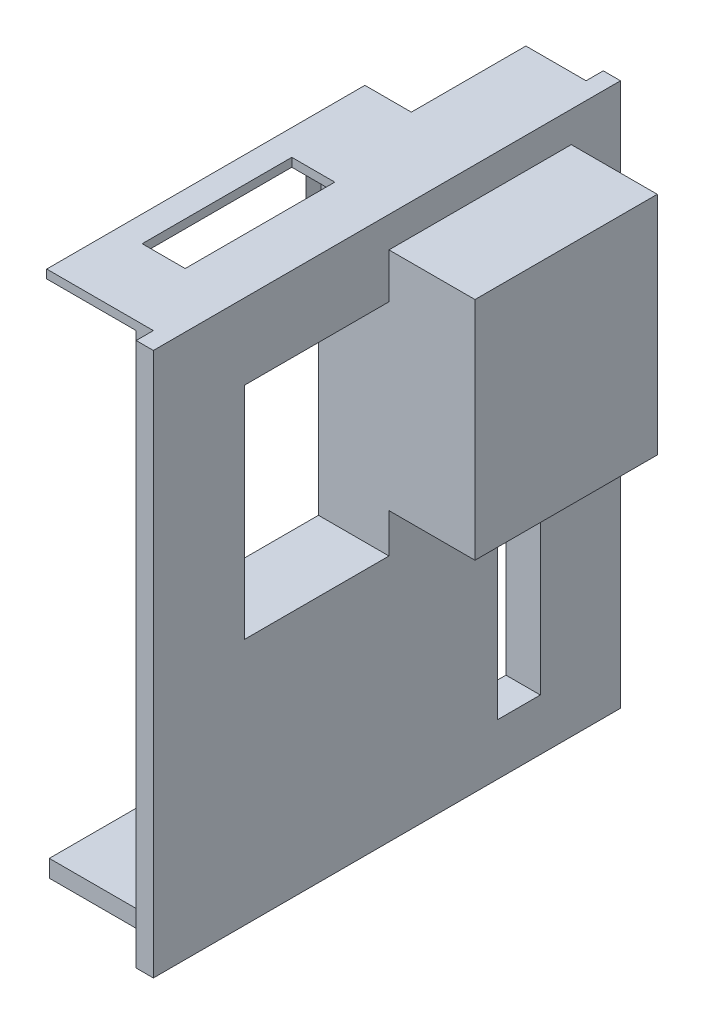
SolidWorks part; units mm, degrees
note: The reader was unsure of these and kept them because the rebuilt part matched: shared geometry of "Sketch1<7>", "Sketch1<9>", "Sketch5<3>", "Sketch5<4>".
ref_plane "Front Plane" through (0, 0, 0) normal (0, 0, 1) x (1, 0, 0)
ref_plane "Top Plane" through (0, 0, 0) normal (0, 1, 0) x (1, 0, 0)
ref_plane "Right Plane" through (0, 0, 0) normal (1, 0, 0) x (0, 0, -1)
sketch "Sketch1" plane through (0, 0, 0) normal (1, 0, 0) x (0, 0, -1)
  line L1 (-14.986, 38.735) -> (32.004, 38.735)
  line L3 (-31.9039, -38.989) -> (32.004, -38.989)
  line L4 (32.004, 38.735) -> (32.004, -38.989)
  line L6 (-31.9039, 38.735) -> (-31.9039, -38.989)
  line L8 (-34.4439, 32.3253) -> (-34.4439, -41.529)
  line L9 (-34.4439, -41.529) -> (34.544, -41.529)
  line L10 (34.544, 38.735) -> (34.544, -41.529)
  line L11 (-31.9039, 38.735) -> (15.0861, 38.735)
  line L12 (-14.986, 38.735) -> (32.004, 38.735)
  line L13 (-31.9039, 38.735) -> (-31.9039, 37.465)
  line L16 (-34.4439, 32.3253) -> (-34.4439, 38.735)
  line L18 (-14.986, 38.735) -> (-31.9039, 38.735)
  line L20 (-34.4439, 38.735) -> (-31.9039, 38.735)
  line L21 (32.004, 38.735) -> (34.544, 38.735)
  line L24 (32.004, 38.735) -> (32.004, 36.195)
  line L25 (-14.986, 38.735) -> (32.004, 38.735)
  line L28 (32.004, 38.735) -> (32.004, 36.195)
  line L29 (-31.9039, 37.465) -> (15.0861, 37.465)
  line L30 (15.0861, 38.735) -> (15.0861, 37.465)
  point P0 (0, 0)
  point P6 (0, 0)
  dimension "D1" = 77.724
  dimension "D2" = 63.9079
  dimension "D3" = 46.99
  dimension "D4" = 1.27
  dimension "D5" = 2.54
  dimension "D6" = 2.54
  dimension "D7" = 2.54
extrude "Boss-Extrude3" add sketch "Sketch1" along normal blind 2.54
extrude "Boss-Extrude4" add sketch "Sketch1<7>" against normal blind 2.54
sketch "Sketch1<7>" plane through (0, 0, 0) normal (1, 0, 0) x (0, 0, -1) same geometry as "Sketch1"
extrude "Boss-Extrude6" add sketch "Sketch1<9>" against normal blind 15.748 contours L13 L29 L30 L11
sketch "Sketch1<9>" plane through (0, 0, 0) normal (1, 0, 0) x (0, 0, -1) same geometry as "Sketch1"
sketch "Sketch2" plane through (0, 38.735, 0) normal (0, 1, 0) x (1, 0, 0)
  line L0 (-15.748, -31.9039) -> (-15.748, 15.0861) construction
  line L1 (-15.748, -21.6169) -> (-5.588, -21.6169)
  line L2 (-15.748, -21.6169) -> (-15.748, 0.4811)
  line L3 (-15.748, 0.4811) -> (-5.588, 0.4811)
  line L4 (-5.588, -21.6169) -> (-5.588, 0.4811)
  line L5 (-15.748, -31.9039) -> (0, -31.9039) construction
  line L6 (-11.938, 0.4811) -> (-11.938, -21.6169)
  dimension "D1" = 10.287
  dimension "D2" = 10.16
  dimension "D3" = 22.098
  dimension "D4" = 3.81
extrude "Cut-Extrude1" cut sketch "Sketch2" against normal blind 2.54 contours L3 L6 L1 L4
sketch "Sketch3" plane through (-2.54, 0, 0) normal (-1, 0, 0) x (0, 0, 1)
  line L1 (-32.004, 38.735) -> (-15.0861, 38.735)
  line L2 (-32.004, 38.735) -> (-32.004, 37.465)
  line L3 (-32.004, 37.465) -> (-15.0861, 37.465)
  line L4 (-15.0861, 38.735) -> (-15.0861, 37.465)
  dimension "D1" = 1.27
extrude "Boss-Extrude7" add sketch "Sketch3" along normal blind 6.35
sketch "Sketch4" plane through (2.54, 0, 0) normal (1, 0, 0) x (0, 0, -1)
  line L0 (-20.9819, 27.559) -> (-20.9819, 38.735) construction
  line L2 (-34.4439, 27.559) -> (-20.9819, 27.559) construction
  line L3 (-34.4439, -41.529) -> (-34.4439, 38.735) construction
  line L4 (-34.4439, 38.735) -> (34.544, 38.735) construction
  line L6 (-20.9819, 27.559) -> (0.3541, 27.559)
  line L7 (-20.9819, 27.559) -> (-20.9819, -4.953)
  line L8 (-20.9819, -4.953) -> (0.3541, -4.953)
  line L9 (0.3541, 27.559) -> (0.3541, -4.953)
  dimension "D1" = 11.176
  dimension "D2" = 13.462
  dimension "D3" = 32.512
  dimension "D4" = 21.336
extrude "Cut-Extrude2" cut sketch "Sketch4" against normal up to surface (5.08 mm away) up to face at (-2.54, -0.762, -0.05)
sketch "Sketch5" plane through (2.54, 0, 0) normal (1, 0, 0) x (0, 0, -1)
  line L0 (-34.4439, 33.401) -> (1.1161, 33.401) construction
  line L1 (-34.4439, -41.529) -> (-34.4439, 38.735) construction
  line L2 (1.1161, 33.401) -> (1.1161, 38.735) construction
  line L3 (-34.4439, 38.735) -> (34.544, 38.735) construction
  line L4 (1.1161, 1.651) -> (26.5161, 33.401) construction
  line L5 (1.1161, 33.401) -> (26.5161, 33.401)
  line L6 (1.1161, 33.401) -> (1.1161, 1.651)
  line L7 (1.1161, 1.651) -> (26.5161, 1.651)
  line L8 (26.5161, 33.401) -> (26.5161, 1.651)
  line L9 (1.1161, 33.401) -> (26.5161, 1.651) construction
  line L10 (0.3541, -4.953) -> (0.3541, 27.559) construction
  line L11 (27.2781, 34.1982) -> (0.3541, 34.1982)
  line L12 (27.2781, 34.1982) -> (27.2781, 0.8538)
  line L13 (27.2781, 0.8538) -> (0.3541, 0.8538)
  line L14 (0.3541, 34.1982) -> (0.3541, 0.8538)
  line L15 (27.2781, 34.1982) -> (0.3541, 0.8538) construction
  line L16 (27.2781, 0.8538) -> (0.3541, 34.1982) construction
  point P10 (13.8161, 17.526)
  dimension "D1" = 35.56
  dimension "D2" = 5.334
  dimension "D3" = 25.4
  dimension "D4" = 31.75
  dimension "D5" = 0.762
extrude "Cut-Extrude3" cut sketch "Sketch5" against normal up to surface (5.08 mm away) contours L8 L5 L6 L7 | L14 L13 L12 L11
extrude "Boss-Extrude8" add sketch "Sketch5<3>" along normal blind 12.7
sketch "Sketch5<3>" plane through (2.54, 0, 0) normal (1, 0, 0) x (0, 0, -1) same geometry as "Sketch5"
extrude "Boss-Extrude9" add sketch "Sketch5<4>" against normal blind 1.27 from offset 12.7 contours L8 L5 L6 L7
sketch "Sketch5<4>" plane through (2.54, 0, 0) normal (1, 0, 0) x (0, 0, -1) same geometry as "Sketch5"
sketch "Sketch7" plane through (-2.54, 0, 0) normal (-1, 0, 0) x (0, 0, 1)
  line L0 (-0.3541, 27.559) -> (-0.3541, -4.953) construction
  line L1 (21.7439, 28.321) -> (-1.1161, 28.321)
  line L2 (21.7439, 28.321) -> (21.7439, -5.715)
  line L3 (21.7439, -5.715) -> (-1.1161, -5.715)
  line L4 (-1.1161, 28.321) -> (-1.1161, -5.715)
  line L5 (-0.3541, -4.953) -> (20.9819, -4.953) construction
  line L6 (20.9819, -4.953) -> (20.9819, 27.559) construction
  line L7 (20.9819, 27.559) -> (-0.3541, 27.559) construction
  line L9 (-0.3541, 27.559) -> (20.9819, 27.559)
  line L10 (-0.3541, 27.559) -> (-0.3541, -4.953)
  line L11 (-0.3541, -4.953) -> (20.9819, -4.953)
  line L12 (20.9819, 27.559) -> (20.9819, -4.953)
  dimension "D1" = 0.762
  dimension "D2" = 0.762
  dimension "D3" = 0.762
  dimension "D4" = 0.762
extrude "Boss-Extrude10" add sketch "Sketch7" along normal blind 5.334
sketch "Sketch6" plane through (-2.54, 0, 0) normal (-1, 0, 0) x (0, 0, 1)
  line L0 (-32.004, 37.465) -> (-15.0861, 37.465) construction
  line L1 (-15.0861, 37.465) -> (-15.0861, -38.989) construction
  line L2 (31.9039, -38.989) -> (-32.004, -38.989) construction
  line L3 (-15.0861, -38.989) -> (-32.004, -38.989) construction
  line L4 (-32.004, -38.989) -> (-32.004, 37.465) construction
  line L5 (-15.0861, -38.989) -> (-32.004, -38.989) construction
  line L6 (-15.0861, -0.889) -> (-32.004, -0.889) construction
  line L12 (-23.545, -0.889) -> (-32.004, -0.889) construction
  line L13 (-32.004, -0.889) -> (-27.7745, -0.889) construction
  line L14 (-27.7745, -0.889) -> (-27.7745, -38.989) construction
  line L16 (-22.7061, -0.889) -> (-16.3561, -0.889)
  line L33 (-22.7061, -0.889) -> (-22.7061, -33.909)
  line L34 (-22.7061, -33.909) -> (-16.3561, -33.909)
  line L35 (-16.3561, -0.889) -> (-16.3561, -33.909)
  dimension "D1" = 1.27
  dimension "D2" = 6.35
  dimension "D3" = 33.02
  dimension "D4" = 38.1
ref_plane "Plane1" through (0, -0.889, 0) normal (0, 1, 0) x (1, 0, 0)
extrude "Cut-Extrude5" cut sketch "Sketch6" against normal blind 5.334
sketch "Sketch9" plane through (-2.54, 0, 0) normal (-1, 0, 0) x (0, 0, 1)
  line L1 (31.9039, -38.989) -> (-11.2761, -38.989)
  line L2 (31.9039, -38.989) -> (31.9039, -36.449)
  line L3 (31.9039, -36.449) -> (-11.2761, -36.449)
  line L4 (-11.2761, -38.989) -> (-11.2761, -36.449)
  dimension "D1" = 2.54
  dimension "D2" = 43.18
extrude "Boss-Extrude12" add sketch "Sketch9" along normal blind 12.827
sketch "Sketch10" plane through (13.97, 0, 0) normal (-1, 0, 0) x (0, 0, 1)
  line L0 (-1.1161, 33.401) -> (-26.5161, 33.401) construction
  line L1 (-13.7145, 31.75) -> (-11.1745, 31.75)
  line L2 (-13.7145, 31.75) -> (-13.7145, 23.622)
  line L3 (-13.7145, 23.622) -> (-11.1745, 23.622)
  line L4 (-11.1745, 31.75) -> (-11.1745, 23.622)
  line L5 (-26.5161, 33.401) -> (-26.5161, 1.651) construction
  dimension "D1" = 15.3416
  dimension "D2" = 1.651
  dimension "D3" = 8.128
  dimension "D4" = 2.54
extrude "Boss-Extrude13" add sketch "Sketch10" along normal blind 32.258
sketch "Sketch11" plane through (0, 31.75, 0) normal (0, 1, 0) x (1, 0, 0)
  line L3 (-18.288, 13.7145) -> (-18.288, 8.952)
  line L4 (-18.288, 8.952) -> (-21.2727, 12.6828)
  line L5 (-20.7768, 13.7145) -> (-18.288, 13.7145)
  arc A0 (-21.2727, 12.6828) -> (-20.7768, 13.7145) centre (-20.7768, 13.0795) cw
  point P5 (-22.098, 13.7145)
  dimension "D3" = 0.635
  dimension "D1" = 4.7625
  dimension "D2" = 3.81
extrude "Boss-Extrude14" add sketch "Sketch11" against normal up to surface (8.128 mm away) up to face at (-2.159, 23.622, -12.4445)
